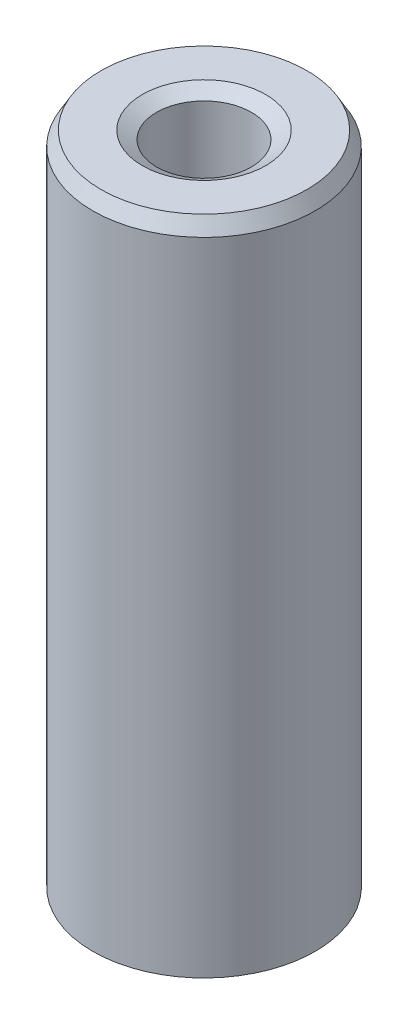
SolidWorks part; units mm, degrees
ref_plane "Front Plane" through (0, 0, 0) normal (0, 0, 1) x (1, 0, 0)
ref_plane "Top Plane" through (0, 0, 0) normal (0, 1, 0) x (1, 0, 0)
ref_plane "Right Plane" through (0, 0, 0) normal (1, 0, 0) x (0, 0, -1)
sketch "Sketch1" plane through (0, 0, 0) normal (0, 1, 0) x (1, 0, 0)
  circle A0 centre (0, 0) radius 20
  dimension "SLEEVE_OD" = 40
extrude "Boss-Extrude1" add sketch "Sketch1" along normal blind 119.3538
sketch "Sketch2" plane through (0, 0, 0) normal (0, 1, 0) x (1, 0, 0)
  circle A0 centre (0, 0) radius 8.5214
  dimension "BORE_D" = 17.0428
extrude "Cut-Extrude1" cut sketch "Sketch2" along normal through all
chamfer "Chamfer1" distance 2.5697 angle 30 4 edges at (0, 119.3538, 8.5214) (0, 0, 8.5214) (0, 0, 20) (0, 119.3538, 20) first distance on face at (0, 119.3538, 8.5214) first distance on face at (0, 0, 8.5214) first distance on face at (0, 119.3538, 20)
